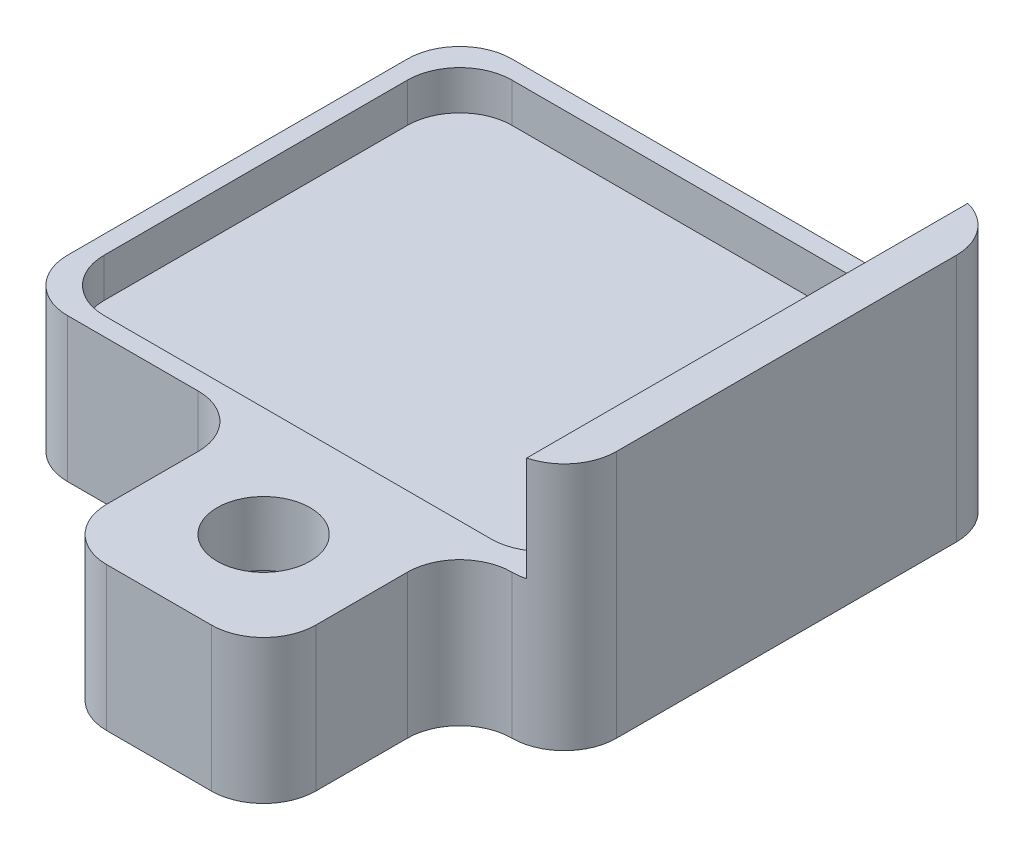
SolidWorks part; units mm, degrees
ref_plane "Front Plane" through (0, 0, 0) normal (0, 0, 1) x (1, 0, 0)
ref_plane "Top Plane" through (0, 0, 0) normal (0, 1, 0) x (1, 0, 0)
ref_plane "Right Plane" through (0, 0, 0) normal (1, 0, 0) x (0, 0, -1)
sketch "Sketch1" plane through (0, 0, 0) normal (0, 1, 0) x (1, 0, 0)
  line L1 (-5.25, -4.25) -> (5.25, -4.25)
  line L2 (-5.25, -4.25) -> (-5.25, 4.25)
  line L3 (-5.25, 4.25) -> (5.25, 4.25)
  line L4 (5.25, -4.25) -> (5.25, 4.25)
  line L5 (-5.25, -4.25) -> (5.25, 4.25) construction
  line L6 (-5.25, 4.25) -> (5.25, -4.25) construction
  point P0 (0, 0)
  dimension "D1" = 10.5
  dimension "D2" = 8.5
extrude "Extrude1" add sketch "Sketch1" along normal blind 4.75
sketch "Sketch3" plane through (0, 4.75, 0) normal (0, 1, 0) x (1, 0, 0)
  line L0 (-5.25, -4.25) -> (5.25, -4.25) construction
  line L1 (-5.25, 4.25) -> (4.5, 4.25)
  line L2 (-5.25, 4.25) -> (-5.25, -4.25)
  line L3 (-5.25, -4.25) -> (4.5, -4.25)
  line L4 (4.5, 4.25) -> (4.5, -4.25)
  dimension "D1" = 9.75
extrude "Extrude4" cut sketch "Sketch3" against normal blind 2
sketch "Sketch4" plane through (0, 2.75, 0) normal (0, 1, 0) x (1, 0, 0)
  line L0 (4.5, -4.25) -> (4.5, 4.25) construction
  line L1 (-4.9, -3.9) -> (4.5, -3.9)
  line L2 (-4.9, -3.9) -> (-4.9, 3.9)
  line L3 (-4.9, 3.9) -> (4.5, 3.9)
  line L4 (4.5, -3.9) -> (4.5, 3.9)
  line L5 (-4.9, -3.9) -> (4.5, 3.9) construction
  line L6 (-4.9, 3.9) -> (4.5, -3.9) construction
  line L7 (-5.25, 4.25) -> (-5.25, -4.25) construction
  line L8 (-5.25, -4.25) -> (4.5, -4.25) construction
  point P0 (-0.0128, -0.1553)
  point P10 (1.3788, -13.3719)
  point P13 (7.4042, -20.1141)
  dimension "D1" = 7.8
  dimension "D2" = 0.35
  dimension "D3" = 0.35
extrude "Extrude5" cut sketch "Sketch4" against normal blind 0.75
sketch "Sketch5" plane through (0, 0, 4.25) normal (0, 0, 1) x (1, 0, 0)
  line L0 (-5.25, 2.75) -> (4.5, 2.75) construction
  line L1 (-0.75, 2.75) -> (3.25, 2.75)
  line L2 (-0.75, 2.75) -> (-0.75, 0)
  line L3 (-0.75, 0) -> (3.25, 0)
  line L4 (3.25, 2.75) -> (3.25, 0)
  line L5 (-5.25, 0) -> (5.25, 0) construction
  line L6 (-5.25, 2.75) -> (-5.25, 0) construction
  dimension "D1" = 4.5
  dimension "D2" = 4
extrude "Extrude6" add sketch "Sketch5" along normal blind 3.75
hole_wizard "CBORE for #0 Socket Head Cap Screw1" positions "3DSketch1" profile "Sketch6" counterbore size "#0" standard "Ansi Inch" end condition through all
sketch3d "3DSketch1"
  line L0 (-0.75, 0, 8) -> (3.25, 0, 8) construction
  line L1 (-0.75, 0, 8) -> (-0.75, 0, 4.25) construction
  point P0 (1.25, 0, 6)
  dimension "D1" = 2
  dimension "D2" = 2
sketch "Sketch6" plane through (1.25, 0, 6) normal (1, 0, 0) x (0, 0, -1)
  line L0 (0, 0) -> (0, 4.75)
  line L1 (0, 4.75) -> (0.889, 4.75)
  line L3 (0.889, 4.75) -> (0.889, 1.524)
  line L4 (0.889, 1.524) -> (1.5875, 1.524)
  line L5 (1.5875, 1.524) -> (1.5875, 0)
  line L7 (1.5875, 0) -> (0, 0)
  line L11 (0, -6.35) -> (0, 107.95) construction
  dimension "Thru Hole Dia." = 1.778
  dimension "Thru Hole Depth" = 4.75
  dimension "C'Bore Dia." = 3.175
  dimension "C'Bore Depth" = 1.524
fillet "Fillet1" radius 1 12 edges at (5.25, 2.375, -4.25) (5.25, 2.375, 4.25) (3.25, 1.375, 8) (-0.75, 1.375, 8) (-5.25, 1.375, -4.25) (-5.25, 1.375, 4.25) (4.5, 2.375, -3.9) (-4.9, 2.375, -3.9) (-4.9, 2.375, 3.9) (4.5, 2.375, 3.9)
